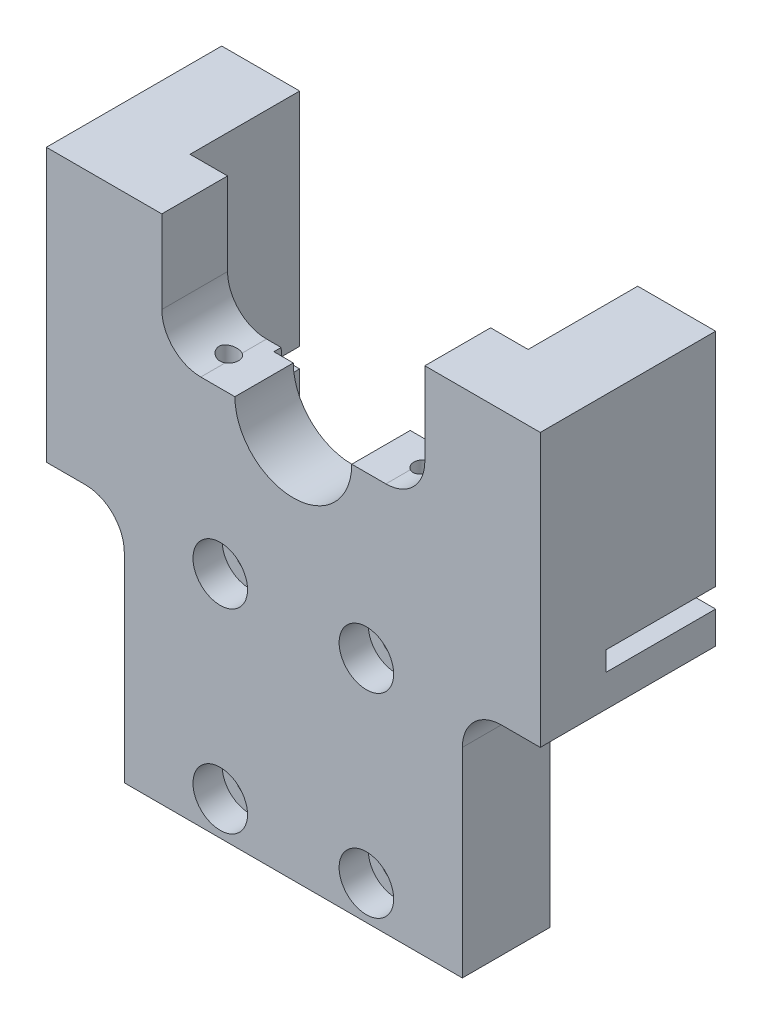
SolidWorks part; units mm, degrees
ref_plane "Front Plane" through (0, 0, 0) normal (0, 0, 1) x (1, 0, 0)
ref_plane "Top Plane" through (0, 0, 0) normal (0, 1, 0) x (1, 0, 0)
ref_plane "Right Plane" through (0, 0, 0) normal (1, 0, 0) x (0, 0, -1)
sketch "Sketch1" plane through (0, 0, 0) normal (0, 0, 1) x (1, 0, 0)
  line L1 (44.5, -23.75) -> (-0.5, -23.75)
  line L2 (44.5, -23.75) -> (44.5, 23.75)
  line L3 (44.5, 23.75) -> (-44.5, 23.75)
  line L4 (-44.5, -23.75) -> (-44.5, 23.75)
  line L5 (44.5, -23.75) -> (-44.5, 23.75) construction
  line L6 (44.5, 23.75) -> (-44.5, -23.75) construction
  line L10 (7.5, 11.75) -> (-32.5, 11.75) construction
  line L12 (-0.5, -23.75) -> (-44.5, -23.75)
  point P0 (0, 0)
  dimension "D1" = 47.5
  dimension "D2" = 89
  dimension "D8" = 40
  dimension "D10" = 12
  dimension "D11" = 12
extrude "Boss-Extrude1" add sketch "Sketch1" along normal mid plane 9
fillet "Fillet1" [suppressed] radius 5
fillet "Fillet2" [suppressed] radius 10
sketch "Sketch2" plane through (0, 0, 4.5) normal (0, 0, 1) x (1, 0, 0)
  line L1 (-44.5, 23.75) -> (-44.5, -23.75) construction
  line L8 (0, 0) -> (0, 23.75) construction
  line L9 (44.5, 23.75) -> (-44.5, 23.75) construction
  line L16 (-44.5, -23.75) -> (44.5, -23.75) construction
  line L17 (18.5, -23.75) -> (21.5, -23.75) construction
  line L18 (18.5, -23.75) -> (18.5, 4.75) construction
  line L19 (20, 3.25) -> (21.5, 3.25) construction
  line L20 (21.5, -23.75) -> (21.5, 4.75) construction
  line L22 (18.5, 4.75) -> (18.5, 3.25) construction
  line L23 (18.5, 3.25) -> (20, 3.25) construction
  line L24 (21.5, 4.75) -> (21.5, 3.25) construction
  line L31 (44.5, -23.75) -> (44.5, 23.75) construction
  line L32 (44.5, 14.25) -> (38, 14.25)
  line L33 (38, 14.25) -> (38, 2.25)
  line L34 (38, 2.25) -> (39.75, 2.25)
  line L35 (39.75, 2.25) -> (39.75, 12.5)
  line L36 (39.75, 12.5) -> (44.5, 12.5)
  line L37 (44.5, 12.5) -> (44.5, 14.25)
  line L38 (-44.5, -23.75) -> (44.5, -23.75) construction
  line L39 (-38, 2.25) -> (-39.75, 2.25)
  line L40 (-39.75, 2.25) -> (-39.75, 12.5)
  line L41 (-39.75, 12.5) -> (-44.5, 12.5)
  line L42 (-44.5, 12.5) -> (-44.5, 14.25)
  line L43 (-44.5, 14.25) -> (-38, 14.25)
  line L44 (-38, 14.25) -> (-38, 2.25)
  arc A8 (18.5, 4.75) -> (21.5, 4.75) centre (20, 4.75) ccw construction
  arc A9 (21.5, 4.75) -> (18.5, 4.75) centre (20, 4.75) ccw construction
  dimension "D5" = 12
  dimension "D6" = 26
  dimension "D1" = 66
  dimension "D2" = 82.5
  dimension "D3" = 1.75
  dimension "D4" = 1.75
  dimension "D8" = 3
  dimension "D9" = 30
extrude "Cut-Extrude1" [suppressed] cut sketch "Sketch2" against normal through all
sketch "Sketch4" plane through (0, 0, 4.5) normal (0, 0, 1) x (1, 0, 0)
  line L0 (44.5, 23.75) -> (-44.5, 23.75) construction
  line L1 (21.5, 23.75) -> (57.0092, 23.75)
  line L2 (21.5, 23.75) -> (21.5, -24.7621)
  line L3 (21.5, -24.7621) -> (57.0092, -24.7621)
  line L4 (57.0092, 23.75) -> (57.0092, -24.7621)
  line L5 (-44.5, 23.75) -> (-44.5, -23.75) construction
  dimension "D1" = 66
  dimension "D2" = 48.5121
  dimension "D3" = 35.5092
extrude "Cut-Extrude2" cut sketch "Sketch4" against normal blind 10
sketch "Sketch5" [suppressed] plane through (0, 0, 2.5) normal (0, 0, 1) x (1, 0, 0)
  line L0 (-38, 2.25) -> (-39.75, 2.25) construction
  line L1 (-38, 14.25) -> (-38, 2.25) construction
  line L2 (-39.75, 2.25) -> (-39.75, 12.5) construction
  line L3 (-39.75, 12.5) -> (-44.5, 12.5) construction
  line L4 (-44.5, 12.5) -> (-44.5, 14.25) construction
  line L5 (-44.5, 14.25) -> (-38, 14.25) construction
  line L6 (-38, 2.25) -> (-39.75, 2.25)
  line L7 (-38, 14.25) -> (-38, 2.25)
  line L8 (-39.75, 2.25) -> (-39.75, 12.5)
  line L9 (-39.75, 12.5) -> (-44.5, 12.5)
  line L10 (-44.5, 12.5) -> (-44.5, 14.25)
  line L11 (-44.5, 14.25) -> (-38, 14.25)
  line L12 (-11.5, 23.75) -> (-11.5, -39.7083) construction
  line L13 (11.5, 23.75) -> (-34.5, 23.75) construction
  line L14 (16.75, 2.25) -> (16.75, 12.5)
  line L15 (15, 14.25) -> (15, 2.25)
  line L16 (15, 2.25) -> (16.75, 2.25)
  line L17 (21.5, 14.25) -> (15, 14.25)
  line L18 (21.5, 12.5) -> (21.5, 14.25)
  line L19 (16.75, 12.5) -> (21.5, 12.5)
  arc A0 (-24.5, -27.75) -> (-0.5, -27.75) centre (-12.5, -27.75) ccw construction
extrude "Cut-Extrude3" [suppressed] cut sketch "Sketch5" against normal blind 10
sketch "Sketch6" plane through (0, 0, 4.5) normal (0, 0, 1) x (1, 0, 0)
  line L0 (21.5, 23.75) -> (-44.5, 23.75) construction
  line L1 (21.5, 23.75) -> (44.5, 23.75)
  line L2 (21.5, 23.75) -> (21.5, -23.75)
  line L3 (21.5, -23.75) -> (44.5, -23.75)
  line L4 (44.5, 23.75) -> (44.5, -23.75)
  line L5 (21.5, 23.75) -> (21.5, -23.75) construction
  dimension "D1" = 23
fillet "Fillet5" [suppressed] radius 10
sketch "Sketch8" plane through (0, 23.75, 0) normal (0, 1, 0) x (1, 0, 0)
  line L4 (-44.5, -4.5) -> (21.5, -4.5)
  line L5 (21.5, -4.5) -> (21.5, 4.5)
  line L6 (21.5, 4.5) -> (-44.5, 4.5)
  line L7 (-44.5, 4.5) -> (-44.5, -4.5)
  line L8 (-44.5, -4.5) -> (21.5, -4.5)
  line L9 (21.5, -4.5) -> (21.5, 4.5)
  line L10 (21.5, 4.5) -> (-44.5, 4.5)
  line L11 (-44.5, 4.5) -> (-44.5, -4.5)
  dimension "D1" = 0
extrude "Boss-Extrude3" add sketch "Sketch8" along normal blind 5
sketch "Sketch9" plane through (0, 28.75, 0) normal (0, 1, 0) x (1, 0, 0)
  line L0 (-44.5, 4.5) -> (-44.5, -4.5) construction
  line L1 (-44.5, -4.5) -> (-28.5, -4.5)
  line L2 (-44.5, -4.5) -> (-44.5, 11.5)
  line L3 (-44.5, 11.5) -> (-28.5, 11.5)
  line L4 (-28.5, -4.5) -> (-28.5, 11.5)
  line L5 (-44.5, -4.5) -> (21.5, -4.5) construction
  line L6 (-11.5, 4.5) -> (-11.5, -4.5) construction
  line L7 (21.5, 4.5) -> (-44.5, 4.5) construction
  line L8 (21.5, 11.5) -> (5.5, 11.5)
  line L9 (5.5, -4.5) -> (5.5, 11.5)
  line L10 (21.5, -4.5) -> (5.5, -4.5)
  line L11 (21.5, -4.5) -> (21.5, 11.5)
  dimension "D1" = 16
  dimension "D2" = 16
extrude "Boss-Extrude4" [suppressed] add sketch "Sketch9" against normal blind 3
sketch "Sketch10" [suppressed] plane through (0, 28.75, 0) normal (0, 1, 0) x (1, 0, 0)
  line L0 (-44.5, 10.5) -> (-39.6498, 10.5)
  line L1 (-44.5, 13.5) -> (-44.5, -2.5) construction
  line L2 (-28.5, 13.5) -> (-44.5, 13.5) construction
  line L3 (-39.6498, 10.5) -> (-39.6498, 3)
  line L4 (-39.6498, 3) -> (-41.6498, 3)
  line L5 (-41.6498, 3) -> (-41.6498, 8.5)
  line L6 (-41.6498, 8.5) -> (-44.5, 8.5)
  line L7 (-44.5, 8.5) -> (-44.5, 10.5)
  line L8 (-11.5, -2.5) -> (-11.5, 2.5) construction
  line L9 (-44.5, -2.5) -> (21.5, -2.5) construction
  line L10 (5.5, 2.5) -> (-28.5, 2.5) construction
  line L11 (21.5, 10.5) -> (16.6498, 10.5)
  line L12 (21.5, 8.5) -> (21.5, 10.5)
  line L13 (18.6498, 8.5) -> (21.5, 8.5)
  line L14 (18.6498, 3) -> (18.6498, 8.5)
  line L15 (16.6498, 3) -> (18.6498, 3)
  line L16 (16.6498, 10.5) -> (16.6498, 3)
  dimension "D1" = 3
  dimension "D2" = 2
  dimension "D3" = 2
  dimension "D4" = 7.5
  dimension "D5" = 2.8502
extrude "Cut-Extrude5" [suppressed] cut sketch "Sketch10" against normal blind 5
fillet "Fillet7" radius 10 2 edges at (21.5, 28.75, 0) (-44.5, 28.75, 0)
sketch "Sketch16" plane through (0, 0, 4.5) normal (0, 0, 1) x (1, 0, 0)
  line L0 (-19, -0.25) -> (-19, -20.25) construction
  line L1 (-19, -20.25) -> (-4, -20.25) construction
  line L2 (-4, -20.25) -> (-4, -0.25) construction
  line L3 (-4, -0.25) -> (-19, -0.25) construction
  line L4 (-44.5, 18.75) -> (-44.5, -23.75) construction
  line L5 (-44.5, -23.75) -> (21.5, -23.75) construction
  line L6 (21.5, 18.75) -> (21.5, -23.75) construction
  circle A0 centre (-19, -0.25) radius 1.5
  circle A1 centre (-4, -0.25) radius 1.5
  circle A2 centre (-19, -20.25) radius 1.5
  circle A3 centre (-4, -20.25) radius 1.5
  dimension "D1" = 3
  dimension "D2" = 20
  dimension "D3" = 15
  dimension "D4" = 3.5
  dimension "D5" = 25.5
extrude "Cut-Extrude6" cut sketch "Sketch16" against normal blind 10
sketch "Sketch17" plane through (0, 0, -4.5) normal (0, 0, -1) x (-1, 0, 0)
  line L0 (44.5, -23.75) -> (-21.5, -23.75) construction
  line L1 (44.5, -23.75) -> (28.85, -23.75)
  line L2 (44.5, -23.75) -> (44.5, 28.75)
  line L3 (44.5, 28.75) -> (28.85, 28.75)
  line L4 (28.85, -23.75) -> (28.85, 28.75)
  line L5 (-11.5, 28.75) -> (34.5, 28.75) construction
  line L6 (44.5, 18.75) -> (44.5, -23.75) construction
  line L7 (11.5, -23.75) -> (11.5, 28.75) construction
  line L8 (-21.5, -23.75) -> (-5.85, -23.75)
  line L9 (-5.85, -23.75) -> (-5.85, 28.75)
  line L10 (-21.5, 28.75) -> (-5.85, 28.75)
  line L11 (-21.5, -23.75) -> (-21.5, 28.75)
  dimension "D1" = 15.65
extrude "Cut-Extrude7" cut sketch "Sketch17" against normal blind 10
sketch "Sketch18" plane through (0, 0, 4.5) normal (0, 0, 1) x (1, 0, 0)
  line L0 (-11.5, 28.75) -> (-11.5, -23.75) construction
  line L1 (-28.85, 28.75) -> (5.85, 28.75) construction
  line L2 (-28.85, -23.75) -> (5.85, -23.75) construction
  circle A0 centre (-11.5, 16.25) radius 6
  dimension "D1" = 12
  dimension "40" = 40
extrude "Cut-Extrude8" cut sketch "Sketch18" against normal blind 10
sketch "Sketch20" plane through (0, 0, 4.5) normal (0, 0, 1) x (1, 0, 0)
  line L0 (-28.85, -23.75) -> (-28.85, 28.75) construction
  line L1 (-28.85, 0.75) -> (-36.85, 0.75)
  line L2 (-28.85, 0.75) -> (-28.85, 28.75)
  line L3 (-28.85, 28.75) -> (-36.85, 28.75)
  line L4 (-36.85, 0.75) -> (-36.85, 28.75)
  line L5 (5.85, 28.75) -> (5.85, -23.75) construction
  line L6 (5.85, 0.75) -> (13.85, 0.75)
  line L7 (5.85, 0.75) -> (5.85, 28.75)
  line L8 (5.85, 28.75) -> (13.85, 28.75)
  line L9 (13.85, 0.75) -> (13.85, 28.75)
  line L11 (-28.85, 28.75) -> (5.85, 28.75) construction
  dimension "D1" = 8
  dimension "D2" = 28
extrude "Boss-Extrude5" add sketch "Sketch20" against normal blind 18
sketch "Sketch22" plane through (0, 0, 4.5) normal (0, 0, 1) x (1, 0, 0)
  line L0 (-25, 16.25) -> (2, 16.25)
  line L1 (2, 16.25) -> (2, 28.75)
  line L2 (-36.85, 28.75) -> (13.85, 28.75) construction
  line L3 (-25, 28.75) -> (-25, 16.25)
  line L4 (-36.85, 28.75) -> (-36.85, 0.75) construction
  circle A0 centre (-11.5, 16.25) radius 8 construction
  point P12 (-11.5, 16.25)
  dimension "D3" = 12.5
  dimension "D4" = 25.35
  dimension "D5" = 16
  dimension "D1" = 27
extrude "Cut-Extrude10" cut sketch "Sketch22" against normal blind 9 and the other way through all
sketch "Sketch23" plane through (0, 0, -4.5) normal (0, 0, -1) x (-1, 0, 0)
  line L0 (-13.85, 0.75) -> (-13.85, 28.75) construction
  line L1 (28.85, -23.75) -> (-5.85, -23.75) construction
  circle A0 centre (11.5, 16.25) radius 8
  dimension "D1" = 16
  dimension "D2" = 25.35
  dimension "D3" = 40
extrude "Cut-Extrude11" cut sketch "Sketch23" against normal blind 3
sketch "Sketch24" plane through (13.85, 0, 0) normal (1, 0, 0) x (0, 0, -1)
  line L0 (-4.5, 6.05) -> (13.5, 6.05) construction
  line L1 (-4.5, 0.75) -> (-4.5, 28.75) construction
  line L2 (13.5, 0.75) -> (13.5, 28.75) construction
  line L3 (13.5, 0.75) -> (-4.5, 0.75) construction
  line L4 (2.25, 6.05) -> (13.5, 6.05)
  line L5 (2.25, 6.05) -> (2.25, 4.05)
  line L6 (2.25, 4.05) -> (13.5, 4.05)
  line L7 (13.5, 6.05) -> (13.5, 4.05)
  dimension "D1" = 2
  dimension "D2" = 3.3
  dimension "D4" = 6.75
extrude "Cut-Extrude12" cut sketch "Sketch24" against normal blind 8 and the other way blind 68.0001 from offset 42.7 offset against normal yes
sketch "Sketch25" plane through (0, 16.25, 0) normal (0, 1, 0) x (1, 0, 0)
  line L0 (-1.5, -1.125) -> (-21.5, -1.125) construction
  line L2 (2, -4.5) -> (2, 4.5) construction
  line L3 (-5.5, -4.5) -> (2, -4.5) construction
  circle A0 centre (-1.5, -1.125) radius 1
  circle A1 centre (-21.5, -1.125) radius 1
  dimension "D1" = 2
  dimension "D2" = 20
  dimension "D4" = 3.5
  dimension "D3" = 3.375
extrude "Cut-Extrude13" cut sketch "Sketch25" against normal blind 12.5
sketch "Sketch26" plane through (0, 0, -4.5) normal (0, 0, -1) x (-1, 0, 0)
  line L9 (-5.85, 6.05) -> (28.85, 6.05)
  line L10 (28.85, 6.05) -> (28.85, 28.75)
  line L11 (28.85, 28.75) -> (25, 28.75)
  line L12 (25, 28.75) -> (25, 16.25)
  line L13 (25, 16.25) -> (19.5, 16.25)
  line L14 (3.5, 16.25) -> (-2, 16.25)
  line L15 (-2, 16.25) -> (-2, 28.75)
  line L16 (-2, 28.75) -> (-5.85, 28.75)
  line L17 (-5.85, 28.75) -> (-5.85, 6.05)
  line L18 (-5.85, 6.05) -> (28.85, 6.05)
  line L19 (28.85, 6.05) -> (28.85, 28.75)
  line L20 (28.85, 28.75) -> (25, 28.75)
  line L21 (25, 28.75) -> (25, 16.25)
  line L22 (25, 16.25) -> (19.5, 16.25)
  line L23 (3.5, 16.25) -> (-2, 16.25)
  line L24 (-2, 16.25) -> (-2, 28.75)
  line L25 (-2, 28.75) -> (-5.85, 28.75)
  line L26 (-5.85, 28.75) -> (-5.85, 6.05)
  arc A1 (3.5, 16.25) -> (19.5, 16.25) centre (11.5, 16.25) ccw
  arc A2 (3.5, 16.25) -> (19.5, 16.25) centre (11.5, 16.25) ccw
  dimension "D1" = 0
extrude "Cut-Extrude15" cut sketch "Sketch26" against normal blind 2.25
fillet "Fillet8" radius 4 4 edges at (2, 16.25, 1.125) (-25, 16.25, 1.125) (-28.85, 0.75, 0) (5.85, 0.75, 0)
sketch "Sketch27" plane through (0, 0, -4.5) normal (0, 0, -1) x (-1, 0, 0)
  line L0 (28.85, -23.75) -> (-5.85, -23.75) construction
  line L1 (22.35, -23.75) -> (0.65, -23.75)
  line L2 (22.35, -23.75) -> (22.35, -16.25)
  line L3 (22.35, -16.25) -> (0.65, -16.25)
  line L4 (0.65, -23.75) -> (0.65, -16.25)
  line L5 (28.85, -3.25) -> (28.85, -23.75) construction
  line L6 (28.85, -10.25) -> (-5.85, -10.25) construction
  line L7 (-5.85, -23.75) -> (-5.85, -3.25) construction
  line L8 (0.65, 3.25) -> (0.65, -4.25)
  line L9 (22.35, 3.25) -> (0.65, 3.25)
  line L10 (22.35, -4.25) -> (0.65, -4.25)
  line L11 (22.35, 3.25) -> (22.35, -4.25)
  dimension "D1" = 7.5
  dimension "D2" = 21.7
  dimension "D3" = 6.5
  dimension "D4" = 13.5
extrude "Cut-Extrude16" cut sketch "Sketch27" against normal blind 0.4
chamfer "Chamfer1" distance 0.4 angle 45 1 edges at (-11.5, -4.25, -4.1)
chamfer "Chamfer2" distance 0.4 angle 45 1 edges at (-11.5, -16.25, -4.1)
sketch "Sketch28" plane through (0, 0, 4.5) normal (0, 0, 1) x (1, 0, 0)
  line L0 (-19, -0.25) -> (-19, -20.25) construction
  line L1 (-19, -20.25) -> (-4, -20.25) construction
  line L2 (-4, -20.25) -> (-4, -0.25) construction
  line L3 (-4, -0.25) -> (-19, -0.25) construction
  line L4 (-28.85, -23.75) -> (-28.85, -3.25) construction
  line L5 (-28.85, -23.75) -> (5.85, -23.75) construction
  circle A0 centre (-19, -0.25) radius 2.8
  circle A1 centre (-4, -0.25) radius 2.8
  circle A2 centre (-4, -20.25) radius 2.8
  circle A3 centre (-19, -20.25) radius 2.8
  dimension "D1" = 5.6
  dimension "D2" = 15
  dimension "D3" = 20
  dimension "D4" = 9.85
  dimension "D5" = 3.5
extrude "Cut-Extrude17" cut sketch "Sketch28" against normal blind 3
sketch "Sketch29" plane through (0, 0, -4.5) normal (0, 0, -1) x (-1, 0, 0)
  line L0 (0.65, -4.25) -> (22.35, -4.25) construction
  line L1 (0.65, 3.25) -> (0.65, -4.25) construction
  line L2 (22.35, -3.85) -> (22.35, 3.25) construction
  line L3 (-5.85, 4.05) -> (28.85, 4.05) construction
  line L4 (0.65, 3.25) -> (22.35, 3.25)
  line L5 (0.65, 3.25) -> (0.65, 4.05)
  line L6 (0.65, 4.05) -> (22.35, 4.05)
  line L7 (22.35, 3.25) -> (22.35, 4.05)
  line L8 (22.35, -4.25) -> (22.35, 3.25) construction
  line L9 (22.35, -16.25) -> (0.65, -16.25) construction
  line L11 (0.65, -16.25) -> (0.65, -23.75) construction
  line L12 (22.35, -23.75) -> (22.35, -16.25) construction
  circle A0 centre (2.65, -4.25) radius 2
  circle A1 centre (20.35, -4.25) radius 2
  circle A2 centre (2.65, -16.25) radius 2
  circle A3 centre (20.35, -16.25) radius 2
  dimension "D1" = 4
extrude "Cut-Extrude18" cut sketch "Sketch29" against normal blind 0.4
